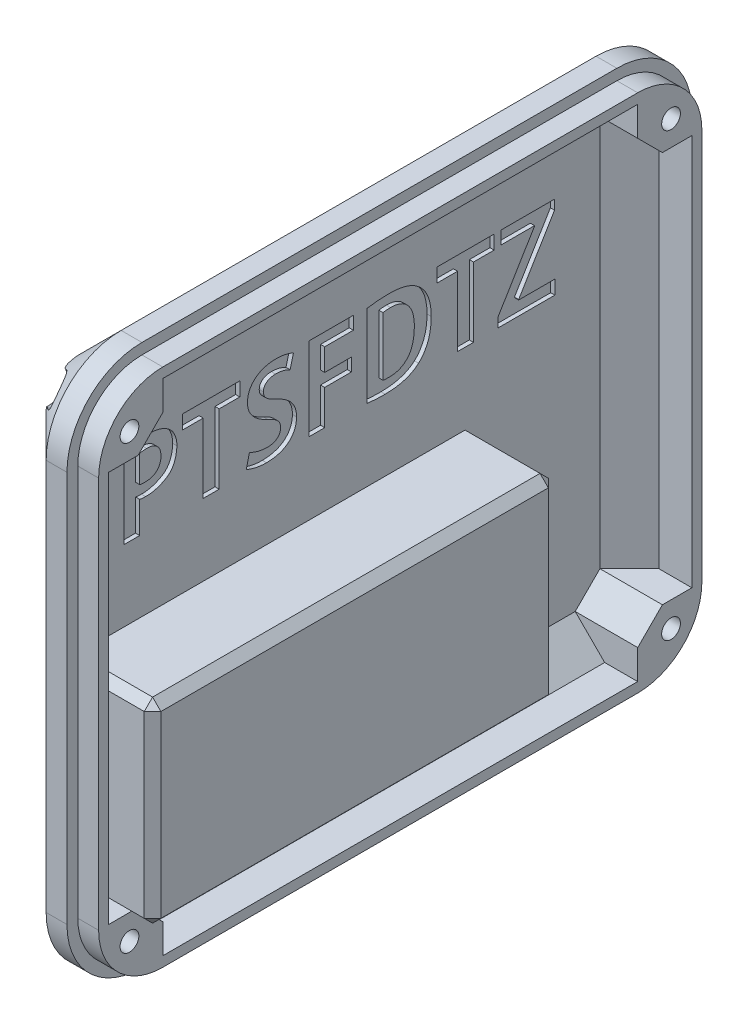
SolidWorks part; units mm, degrees
ref_plane "前视基准面" through (0, 0, 0) normal (0, 0, 1) x (1, 0, 0)
ref_plane "上视基准面" through (0, 0, 0) normal (0, 1, 0) x (1, 0, 0)
ref_plane "右视基准面" through (0, 0, 0) normal (1, 0, 0) x (0, 0, -1)
other "Configuration Table"
sketch "草图3" plane through (0, 0, 0) normal (1, 0, 0) x (0, 0, -1)
  line L1 (-57, -65) -> (57, -65)
  line L2 (-75, -47) -> (-75, 47)
  line L3 (-57, 65) -> (57, 65)
  line L4 (75, -47) -> (75, 47)
  line L5 (-75, -65) -> (75, 65) construction
  line L6 (-75, 65) -> (75, -65) construction
  arc A0 (57, -65) -> (75, -47) centre (57, -47) ccw
  arc A1 (-75, 47) -> (-57, 65) centre (-57, 47) cw
  arc A2 (-57, -65) -> (-75, -47) centre (-57, -47) cw
  arc A3 (57, 65) -> (75, 47) centre (57, 47) cw
  point P0 (0, 0)
  dimension "D3" = 18
  dimension "D1" = 150
  dimension "D2" = 130
extrude "凸台-拉伸4" add sketch "草图3" along normal blind 15
chamfer "倒角2" distance 10 angle 45 8 edges at (0, 0, -75) (0, 59.7279, -69.7279) (0, 65, 0) (0, 59.7279, 69.7279) (0, 0, 75) (0, -59.7279, 69.7279) (0, -65, 0) (0, -59.7279, -69.7279)
shell "抽壳3" thickness 5 removed face at (15, 0, 0)
sketch "草图4" plane through (15, 0, 0) normal (1, 0, 0) x (0, 0, -1)
  line L17 (70, -47) -> (70, 47)
  line L18 (57, 60) -> (-57, 60)
  line L19 (-70, 47) -> (-70, -47)
  line L20 (72.4, -47) -> (72.4, 47)
  line L21 (-57, -62.4) -> (57, -62.4)
  line L22 (-72.4, 47) -> (-72.4, -47)
  line L23 (57, 62.4) -> (-57, 62.4)
  line L24 (72.4, -47) -> (72.4, 47)
  line L25 (-57, -62.4) -> (57, -62.4)
  line L26 (-72.4, 47) -> (-72.4, -47)
  line L27 (57, 62.4) -> (-57, 62.4)
  line L28 (-57, -60) -> (57, -60)
  arc A22 (70, 47) -> (57, 60) centre (57, 47) ccw
  arc A23 (-57, 60) -> (-70, 47) centre (-57, 47) ccw
  arc A24 (57, -62.4) -> (72.4, -47) centre (57, -47) ccw
  arc A25 (-72.4, -47) -> (-57, -62.4) centre (-57, -47) ccw
  arc A26 (-57, 62.4) -> (-72.4, 47) centre (-57, 47) ccw
  arc A27 (72.4, 47) -> (57, 62.4) centre (57, 47) ccw
  arc A28 (57, -62.4) -> (72.4, -47) centre (57, -47) ccw
  arc A29 (-72.4, -47) -> (-57, -62.4) centre (-57, -47) ccw
  arc A30 (-57, 62.4) -> (-72.4, 47) centre (-57, 47) ccw
  arc A31 (72.4, 47) -> (57, 62.4) centre (57, 47) ccw
  arc A32 (-70, -47) -> (-57, -60) centre (-57, -47) ccw
  arc A33 (57, -60) -> (70, -47) centre (57, -47) ccw
  dimension "D1" = 2.4
  dimension "D2" = 2.4
extrude "凸台-拉伸5" add sketch "草图4" along normal blind 5
sketch "草图5" plane through (20, 0, 0) normal (1, 0, 0) x (0, 0, -1)
  line L0 (-57, 52.9289) -> (-62.9289, 47)
  line L1 (-62.9289, -47) -> (-62.9289, 47) construction
  line L2 (-62.9289, 47) -> (-70, 47)
  line L3 (-57, 60) -> (-57, 52.9289)
  line L4 (0, 0) -> (0, 60) construction
  line L5 (57, 60) -> (-57, 60) construction
  line L6 (0, 0) -> (-70, 0) construction
  line L7 (-70, 47) -> (-70, -47) construction
  line L8 (57, 60) -> (57, 52.9289)
  line L9 (57, 52.9289) -> (62.9289, 47)
  line L10 (62.9289, 47) -> (70, 47)
  line L11 (62.9289, -47) -> (70, -47)
  line L12 (57, -52.9289) -> (62.9289, -47)
  line L13 (57, -60) -> (57, -52.9289)
  line L14 (-57, -60) -> (-57, -52.9289)
  line L15 (-57, -52.9289) -> (-62.9289, -47)
  line L16 (-62.9289, -47) -> (-70, -47)
  arc A0 (-57, 52.9289) -> (-62.9289, 47) centre (-57, 47) ccw construction
  arc A1 (-57, 60) -> (-70, 47) centre (-57, 47) ccw
  arc A2 (57, 60) -> (70, 47) centre (57, 47) cw
  arc A3 (57, -60) -> (70, -47) centre (57, -47) ccw
  arc A4 (-57, -60) -> (-70, -47) centre (-57, -47) cw
extrude "凸台-拉伸6" add sketch "草图5" against normal up to next
sketch "草图6" plane through (20, 0, 0) normal (1, 0, 0) x (0, 0, -1)
  line L0 (57, 65) -> (-57, 65) construction
  line L1 (75, -47) -> (75, 47) construction
  line L2 (0, 0) -> (0, 60) construction
  line L3 (57, 60) -> (-57, 60) construction
  line L4 (0, 0) -> (-70, 0) construction
  line L5 (-70, 47) -> (-70, -47) construction
  circle A0 centre (65, 53) radius 2.25
  circle A1 centre (-65, 53) radius 2.25
  circle A2 centre (65, -53) radius 2.25
  circle A3 centre (-65, -53) radius 2.25
  dimension "D1" = 4.5
  dimension "D2" = 12
  dimension "D3" = 10
extrude "切除-拉伸1" cut sketch "草图6" against normal blind 43
sketch "草图7" plane through (0, 0, 0) normal (-1, 0, 0) x (0, 0, 1)
  line L0 (0, 0) -> (0, 55) construction
  line L1 (57, 55) -> (-57, 55) construction
  line L2 (0, 0) -> (-65, 0) construction
  line L3 (-65, 47) -> (-65, -47) construction
  circle A0 centre (65, 53) radius 3.75
  circle A1 centre (-65, 53) radius 3.75
  circle A2 centre (-65, -53) radius 3.75
  circle A3 centre (65, -53) radius 3.75
  dimension "D1" = 7.5
extrude "切除-拉伸2" cut sketch "草图7" against normal blind 16
fillet "圆角1" radius 2 4 edges at (0, -50.75, 62) (0, -50.75, -62) (0, 50.75, -62) (0, 50.75, 62)
sketch "草图8" plane through (0, 0, 0) normal (-1, 0, 0) x (0, 0, 1)
  line L0 (-57, -55) -> (57, -55) construction
  line L1 (-30.5511, -47) -> (62.4489, -47)
  line L2 (-30.5511, -47) -> (-30.5511, -4)
  line L3 (-30.5511, -4) -> (62.4489, -4)
  line L4 (62.4489, -47) -> (62.4489, -4)
  line L5 (-30.5511, -47) -> (62.4489, -4) construction
  line L6 (-30.5511, -4) -> (62.4489, -47) construction
  point P0 (15.9489, -25.5)
  dimension "D1" = 43
  dimension "D2" = 93
  dimension "D3" = 8
extrude "切除-拉伸3" cut sketch "草图8" against normal blind 16
sketch "草图12" plane through (5, 0, 0) normal (1, 0, 0) x (0, 0, -1)
  line L0 (-64.4489, -2) -> (-64.4489, -49)
  line L1 (-62.4489, -4) -> (30.5511, -4)
  line L2 (-62.4489, -4) -> (-62.4489, -47)
  line L3 (-62.4489, -47) -> (30.5511, -47)
  line L4 (30.5511, -4) -> (30.5511, -47)
  line L5 (-64.4489, -49) -> (32.5511, -49)
  line L6 (32.5511, -2) -> (32.5511, -49)
  line L7 (-64.4489, -2) -> (32.5511, -2)
  dimension "D1" = 2
extrude "凸台-拉伸7" add sketch "草图12" along normal blind 18
sketch "草图14" plane through (23, 0, 0) normal (1, 0, 0) x (0, 0, -1)
  line L1 (-64.4489, -2) -> (32.5511, -2)
  line L2 (-64.4489, -2) -> (-64.4489, -49)
  line L3 (-64.4489, -49) -> (32.5511, -49)
  line L4 (32.5511, -2) -> (32.5511, -49)
extrude "凸台-拉伸8" add sketch "草图14" along normal blind 2
chamfer "倒角4" distance 2 angle 45 8 edges at (25, -2, 15.9489) (15, -2, -32.5511) (25, -25.5, -32.5511) (15, -49, -32.5511) (25, -49, 15.9489) (22.5, -49, 64.4489) (25, -25.5, 64.4489) (15.76, -2, 64.4489)
sketch "草图15" plane through (0, 0, 0) normal (-1, 0, 0) x (0, 0, 1)
  line L0 (-57, -55) -> (57, -55) construction
  line L1 (-30.5511, -4) -> (-22.5511, -4)
  line L2 (-30.5511, -4) -> (-30.5511, 4)
  line L3 (-30.5511, 4) -> (-22.5511, 4)
  line L4 (-22.5511, -4) -> (-22.5511, 4)
  line L5 (-30.5511, -47) -> (-22.5511, -47)
  line L6 (-30.5511, -47) -> (-30.5511, -55)
  line L7 (-30.5511, -55) -> (-22.5511, -55)
  line L8 (-22.5511, -47) -> (-22.5511, -55)
  line L10 (62.4489, -4) -> (54.4489, -4)
  line L11 (62.4489, -4) -> (62.4489, 4)
  line L12 (62.4489, 4) -> (54.4489, 4)
  line L13 (54.4489, -4) -> (54.4489, 4)
  dimension "D1" = 8
  dimension "D2" = 8
  dimension "D3" = 8
  dimension "D4" = 8
  dimension "D5" = 8
extrude "切除-拉伸4" cut sketch "草图15" against normal blind 3
fillet "圆角2" radius 4 6 edges at (1.5, 4, 62.4489) (1.5, 4, 54.4489) (1.5, -55, -22.5511) (1.5, -55, -30.5511) (1.5, 4, -22.5511) (1.5, 4, -30.5511)
sketch "草图17" plane through (5, 0, 0) normal (1, 0, 0) x (0, 0, -1)
  text T0 "<b>PTSFDTZ</b>" font "@Adobe Gothic Std B" height 20
extrude "切除-拉伸5" cut sketch "草图17" against normal blind 1
sketch "草图18" plane through (0, 0, -30.5511) normal (0, 0, 1) x (1, 0, 0)
  line L0 (5, -4) -> (23, -4) construction
  line L1 (23, -4) -> (23, -47) construction
  circle A0 centre (12, -12) radius 5
  dimension "D2" = 11
  dimension "D3" = 10
  dimension "D1" = 8
extrude "切除-拉伸6" cut sketch "草图18" against normal blind 10
